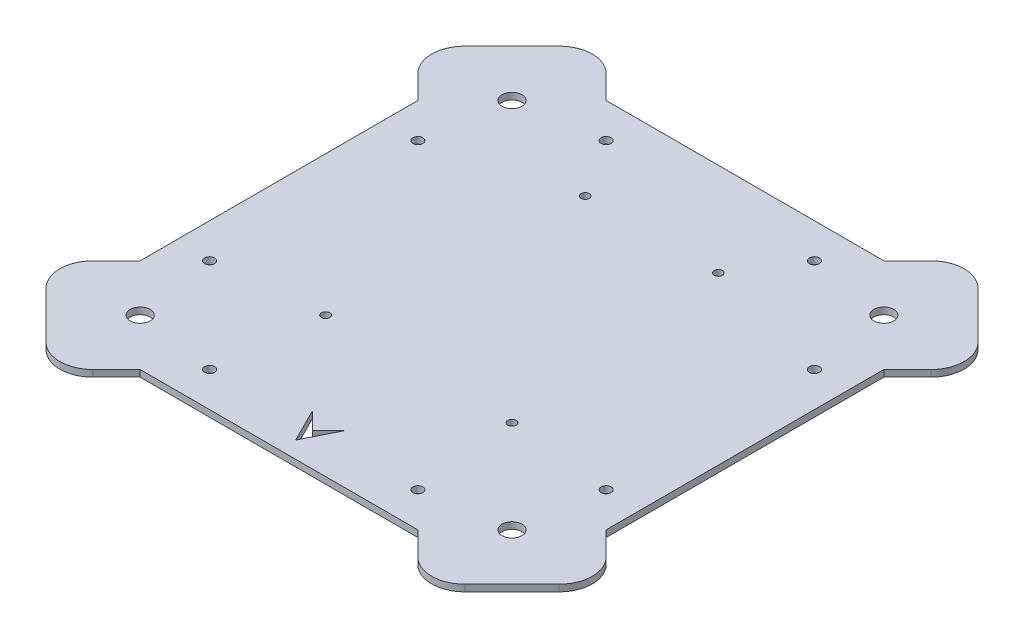
SolidWorks part; units mm, degrees
ref_plane "Front Plane" through (0, 0, 0) normal (0, 0, 1) x (1, 0, 0)
ref_plane "Top Plane" through (0, 0, 0) normal (0, 1, 0) x (1, 0, 0)
ref_plane "Right Plane" through (0, 0, 0) normal (1, 0, 0) x (0, 0, -1)
sketch "Sketch1" plane through (0, 0, 0) normal (0, 1, 0) x (1, 0, 0)
  line L1 (0, 0) -> (140, 0)
  line L2 (0, 0) -> (0, 140)
  line L3 (0, 140) -> (140, 140)
  line L4 (140, 0) -> (140, 140)
  dimension "D1" = 140
  dimension "D2" = 140
extrude "Boss-Extrude1" add sketch "Sketch1" along normal blind 2
sketch "Sketch2" plane through (0, 2, 0) normal (0, 1, 0) x (1, 0, 0)
  line L0 (70, 140) -> (70, 0) construction
  line L1 (140, 140) -> (0, 140) construction
  line L2 (0, 0) -> (140, 0) construction
  line L3 (140, 70) -> (0, 70) construction
  line L4 (140, 0) -> (140, 140) construction
  line L5 (0, 140) -> (0, 0) construction
  line L6 (70, 70) -> (140, 140) construction
  line L7 (125.8579, 125.8579) -> (140, 111.7157) construction
  line L8 (125.8579, 125.8579) -> (111.7157, 140) construction
  line L9 (111.7157, 140) -> (140, 111.7157)
  line L10 (111.7157, 140) -> (125.8579, 154.1421)
  line L11 (140, 111.7157) -> (154.1421, 125.8579)
  line L12 (125.8579, 154.1421) -> (154.1421, 125.8579)
  line L13 (0, 111.7157) -> (-14.1421, 125.8579)
  line L14 (14.1421, 154.1421) -> (-14.1421, 125.8579)
  line L15 (28.2843, 140) -> (14.1421, 154.1421)
  line L16 (28.2843, 140) -> (0, 111.7157)
  line L17 (28.2843, 0) -> (0, 28.2843)
  line L18 (28.2843, 0) -> (14.1421, -14.1421)
  line L19 (14.1421, -14.1421) -> (-14.1421, 14.1421)
  line L20 (0, 28.2843) -> (-14.1421, 14.1421)
  line L21 (140, 28.2843) -> (154.1421, 14.1421)
  line L22 (125.8579, -14.1421) -> (154.1421, 14.1421)
  line L23 (111.7157, 0) -> (125.8579, -14.1421)
  line L24 (111.7157, 0) -> (140, 28.2843)
  point P33 (140, 111.7157)
  point P34 (111.7157, 140)
  dimension "D1" = 40
  dimension "D2" = 20
extrude "Boss-Extrude3" add sketch "Sketch2" against normal blind 2
fillet "Fillet1" radius 10 8 edges at (154.1421, 1, -14.1421) (125.8579, 1, 14.1421) (14.1421, 1, 14.1421) (-14.1421, 1, -14.1421) (-14.1421, 1, -125.8579) (14.1421, 1, -154.1421) (125.8579, 1, -154.1421) (154.1421, 1, -125.8579)
sketch "Sketch4" plane through (0, 2, 0) normal (0, 1, 0) x (1, 0, 0)
  line L0 (70, 140) -> (70, 0) construction
  line L1 (111.7157, 140) -> (28.2843, 140) construction
  line L2 (28.2843, 0) -> (111.7157, 0) construction
  line L3 (0, 70) -> (140, 70) construction
  line L4 (0, 111.7157) -> (0, 28.2843) construction
  line L5 (140, 28.2843) -> (140, 111.7157) construction
  line L6 (28.2843, 0) -> (70, 41.7157) construction
  line L7 (35.0089, 35.0089) -> (6.7246, 6.7246) construction
  circle A0 centre (38.7176, 10.4334) radius 1.5
  circle A1 centre (10.4334, 38.7176) radius 1.5
  circle A2 centre (101.2824, 10.4334) radius 1.5
  circle A3 centre (129.5666, 38.7176) radius 1.5
  circle A4 centre (38.7176, 129.5666) radius 1.5
  circle A5 centre (10.4334, 101.2824) radius 1.5
  circle A6 centre (101.2824, 129.5666) radius 1.5
  circle A7 centre (129.5666, 101.2824) radius 1.5
  point P17 (0, 0)
  point P23 (0, 0)
  dimension "D1" = 3
  dimension "D2" = 10.4334
extrude "Cut-Extrude2" cut sketch "Sketch4" against normal blind 2
sketch "Sketch5" plane through (0, 2, 0) normal (0, 1, 0) x (1, 0, 0)
  line L0 (0, 28.2843) -> (28.2843, 0) construction
  line L1 (70, 140) -> (70, 0) construction
  line L2 (111.7157, 140) -> (28.2843, 140) construction
  line L3 (28.2843, 0) -> (111.7157, 0) construction
  line L4 (0, 70) -> (140, 70) construction
  line L5 (0, 111.7157) -> (0, 28.2843) construction
  line L6 (140, 28.2843) -> (140, 111.7157) construction
  circle A0 centre (14.1421, 14.1421) radius 3
  circle A1 centre (125.8579, 14.1421) radius 3
  circle A2 centre (14.1421, 125.8579) radius 3
  circle A3 centre (125.8579, 125.8579) radius 3
  dimension "D1" = 6
extrude "Cut-Extrude3" cut sketch "Sketch5" against normal blind 10
sketch "Sketch6" plane through (0, 2, 0) normal (0, 1, 0) x (1, 0, 0)
  line L0 (70, 140) -> (70, 0) construction
  line L1 (111.7157, 140) -> (28.2843, 140) construction
  line L2 (28.2843, 0) -> (111.7157, 0) construction
  line L3 (0, 70) -> (140, 70) construction
  line L4 (0, 111.7157) -> (0, 28.2843) construction
  line L5 (140, 28.2843) -> (140, 111.7157) construction
  line L6 (70, 112) -> (90, 112) construction
  line L7 (70, 42) -> (98, 42) construction
  circle A0 centre (90, 112) radius 1.25
  circle A1 centre (98, 42) radius 1.25
  circle A2 centre (42, 42) radius 1.25
  circle A3 centre (50, 112) radius 1.25
  point P22 (70, 70)
  dimension "D1" = 2.5
  dimension "D2" = 40
  dimension "D4" = 56
  dimension "D3" = 70
  dimension "D5" = 39.598
extrude "Cut-Extrude4" cut sketch "Sketch6" against normal blind 15
sketch "Sketch7" plane through (0, 2, 0) normal (0, 1, 0) x (1, 0, 0)
  line L0 (70, 0) -> (70, 140) construction
  line L1 (28.2843, 0) -> (111.7157, 0) construction
  line L2 (111.7157, 140) -> (28.2843, 140) construction
  line L3 (70, 15) -> (75, 15) construction
  line L4 (75, 15) -> (70, 5)
  line L5 (70, 10) -> (75, 15)
  line L6 (65, 15) -> (70, 5)
  line L7 (70, 10) -> (65, 15)
  point P8 (70, 5)
  point P9 (70, 10)
  dimension "D1" = 5
  dimension "D2" = 10
  dimension "D3" = 5
  dimension "D4" = 5
extrude "Cut-Extrude5" cut sketch "Sketch7" against normal blind 2
